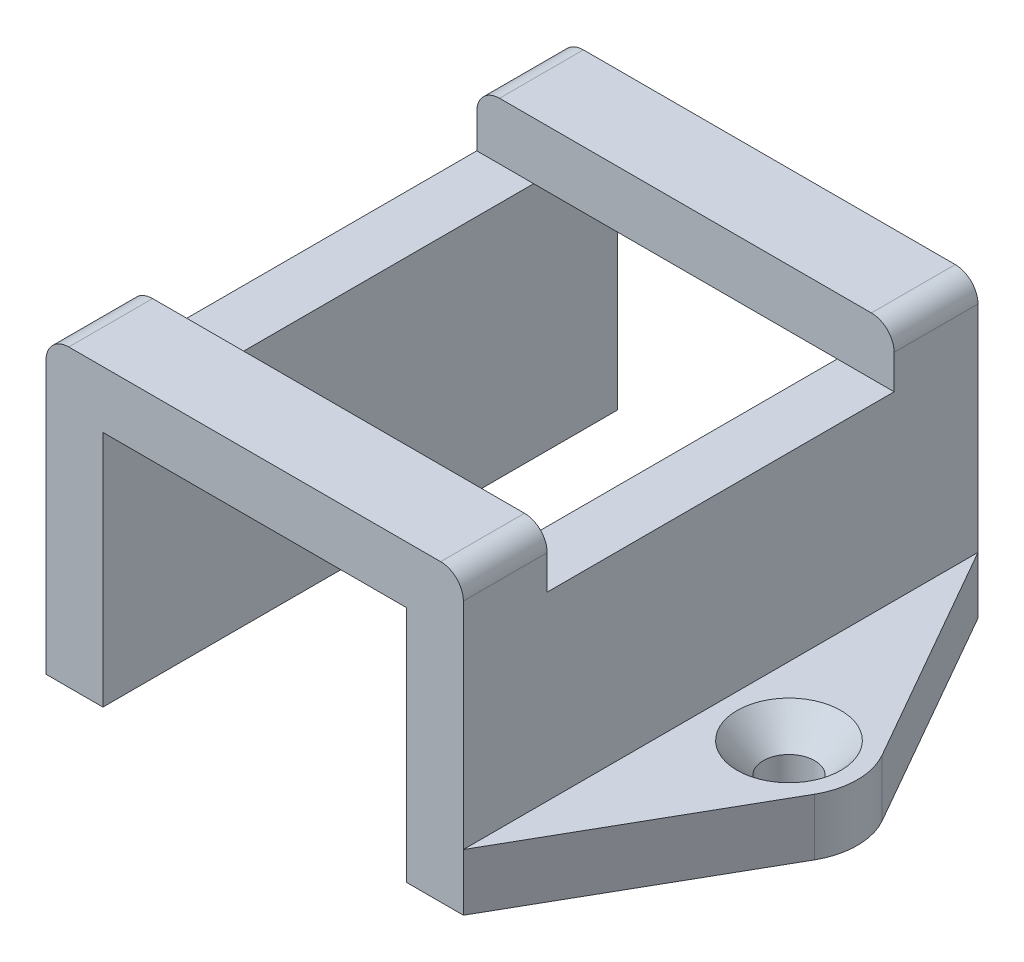
SolidWorks part; units mm, degrees
ref_plane "Front Plane" through (0, 0, 0) normal (0, 0, 1) x (1, 0, 0)
ref_plane "Top Plane" through (0, 0, 0) normal (0, 1, 0) x (1, 0, 0)
ref_plane "Right Plane" through (0, 0, 0) normal (1, 0, 0) x (0, 0, -1)
ref_axis "X" through (-88.99, 0, 0) along (1, 0, 0)
ref_axis "Y" through (0, 55, 0) along (0, -1, 0)
ref_axis "Z" through (0, 0, -88.99) along (0, 0, 1)
sketch "Sketch1" plane through (0, 0, 0) normal (0, 0, 1) x (1, 0, 0)
  line L0 (0, 20.9042) -> (13.335, 20.9042)
  line L1 (13.335, 20.9042) -> (13.335, 0)
  line L2 (13.335, 0) -> (30.335, 0)
  line L3 (30.335, 0) -> (30.335, 5)
  line L4 (30.335, 5) -> (18.335, 5)
  line L5 (18.335, 5) -> (18.335, 25.9042)
  line L6 (18.335, 25.9042) -> (0, 25.9042)
  line L7 (0, 25.9042) -> (0, 20.9042)
  dimension "D1" = 20.9042
  dimension "D2" = 13.335
  dimension "D3" = 5
  dimension "D4" = 5
  dimension "D5" = 5
  dimension "D6" = 12
extrude "Boss-Extrude1" add sketch "Sketch1" along normal mid plane 45.212
sketch "Sketch2" plane through (0, 20.9042, 0) normal (0, -1, 0) x (1, 0, 0)
  line L0 (0, 22.606) -> (0, -22.606) construction
  line L1 (0, 15.24) -> (32.6366, 15.24)
  line L2 (0, 15.24) -> (0, -15.24)
  line L3 (0, -15.24) -> (32.6366, -15.24)
  line L4 (32.6366, 15.24) -> (32.6366, -15.24)
  dimension "D1" = 30.48
extrude "Cut-Extrude1" cut sketch "Sketch2" against normal through all
hole_wizard "CSK for #8 Flat Head Socket Cap Screw1" positions "Sketch3" profile "Sketch4" countersink size "#8" standard "ANSI Inch" end condition through all
sketch "Sketch3" plane through (0, 5, 0) normal (0, 1, 0) x (1, 0, 0)
  line L0 (30.335, 22.606) -> (18.335, 22.606) construction
  point P0 (24.335, 0)
  point P5 (24.335, 22.606)
sketch "Sketch4" plane through (24.335, 5, 0) normal (1, 0, 0) x (0, 0, 1)
  line L0 (0, 0) -> (0, 5)
  line L1 (0, 5) -> (2.2479, 5)
  line L2 (2.2479, 5) -> (2.2479, 2.659)
  line L3 (2.2479, 2.659) -> (4.5593, 0)
  line L5 (4.5593, 0) -> (0, 0)
  line L6 (-2.2479, 2.659) -> (-4.5593, 0) construction
  line L11 (0, -6.35) -> (0, 107.95) construction
  dimension "Thru Hole Dia." = 4.4958
  dimension "Thru Hole Depth" = 5
  dimension "Near C'Sink Dia." = 9.1186
  dimension "Near C'Sink Angle" = 82
sketch "Sketch5" plane through (0, 5, 0) normal (0, 1, 0) x (1, 0, 0)
  line L0 (18.335, 22.606) -> (30.335, 22.606)
  line L1 (30.335, 22.606) -> (30.335, -22.606)
  line L2 (30.335, -22.606) -> (18.335, -22.606)
  line L3 (18.335, -22.606) -> (29.5453, -2.9754)
  line L4 (29.5453, 2.9754) -> (18.335, 22.606)
  arc A0 (29.5453, -2.9754) -> (29.5453, 2.9754) centre (24.335, 0) ccw
  line M4 (30.335, 22.606) -> (18.335, 22.606)
  line M6 (18.335, -22.606) -> (30.335, -22.606)
  line M7 (30.335, -22.606) -> (30.335, 22.606)
extrude "Cut-Extrude2" cut sketch "Sketch5" against normal through all contours A0 L1 L4 M4 | A0 L3 M6 M7 region at (26.3415, 5, 15.5775) region at (26.3415, 5, -15.5775)
fillet "Fillet1" radius 2 2 edges at (18.335, 25.9042, -18.923) (18.335, 25.9042, 18.923)
mirror "Mirror1" about plane through (0, 0, 0) normal (1, 0, 0) of bodies 106
